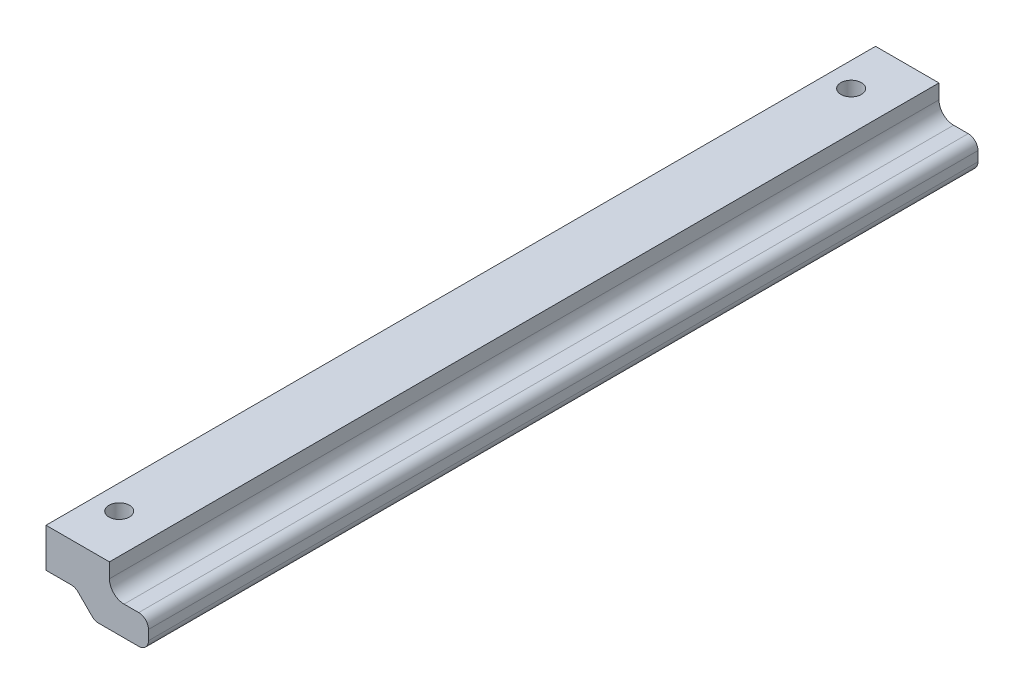
SolidWorks part; units mm, degrees
ref_plane "Front Plane" through (0, 0, 0) normal (0, 0, 1) x (1, 0, 0)
ref_plane "Top Plane" through (0, 0, 0) normal (0, 1, 0) x (1, 0, 0)
ref_plane "Right Plane" through (0, 0, 0) normal (1, 0, 0) x (0, 0, -1)
sketch "Sketch1" plane through (0, 0, 0) normal (0, 0, 1) x (1, 0, 0)
  line L1 (13, -6) -> (13, 0)
  line L2 (55, 0) -> (-55, 0) construction
  line L6 (13, -6) -> (21, -6)
  line L7 (21, -6) -> (21, -12)
  line L8 (0, 0) -> (13, 0)
  line L9 (21, -12) -> (10, -12)
  line L10 (10, -12) -> (6, -8)
  line L11 (6, -8) -> (0, -8)
  line L13 (0, -55) -> (0, 55) construction
  line L14 (0, -8) -> (0, 0)
  point P0 (9.4314, -8)
  dimension "D1" = 6
  dimension "D2" = 6
  dimension "D3" = 8
  dimension "D4" = 10
  dimension "D5" = 8
  dimension "D6" = 45
extrude "Boss-Extrude1" add sketch "Sketch1" against normal blind 170 contours L7 L6 region at (9.8798, -6.062, 0)
fillet "Fillet2" radius 3 1 edges at (13, -6, -85)
sketch "Sketch2" plane through (0, 0, 0) normal (0, 1, 0) x (1, 0, 0)
  line L0 (0, -55) -> (0, 55) construction
  line L1 (-55, 0) -> (55, 0) construction
  circle A0 centre (5, 10) radius 2.1
  circle A1 centre (5, 160) radius 2.1
  dimension "D3" = 4.2
  dimension "D1" = 5
  dimension "D2" = 10
  dimension "D4" = 150
extrude "Cut-Extrude1" cut sketch "Sketch2" against normal up to surface (8 mm away) up to face at (3, -8, -85)
sketch "Sketch3" plane through (0, 0, 0) normal (0, 1, 0) x (1, 0, 0)
  line L0 (0, -55) -> (0, 55) construction
  line L1 (1.55, 11.9919) -> (1.55, 8.0081)
  line L16 (1.55, 8.0081) -> (5, 6.0163)
  line L17 (5, 6.0163) -> (8.45, 8.0081)
  line L18 (8.45, 8.0081) -> (8.45, 11.9919)
  line L19 (8.45, 11.9919) -> (5, 13.9837)
  line L20 (5, 13.9837) -> (1.55, 11.9919)
  line L22 (1.55, 161.9919) -> (1.55, 158.0081)
  line L23 (1.55, 158.0081) -> (5, 156.0163)
  line L24 (5, 156.0163) -> (8.45, 158.0081)
  line L25 (8.45, 158.0081) -> (8.45, 161.9919)
  line L26 (8.45, 161.9919) -> (5, 163.9837)
  line L27 (5, 163.9837) -> (1.55, 161.9919)
  circle A2 centre (5, 10) radius 3.45 construction
  circle A3 centre (5, 160) radius 3.45 construction
  dimension "D1" = 6.9
  dimension "D2" = 6.9
extrude "Cut-Extrude2" cut sketch "Sketch3" along normal blind 8 from surface starting at face at (15.5, -12, -85)
fillet "Fillet3" radius 2 2 edges at (21, -12, -85) (21, -6, -85)
sketch "Sketch4" plane through (0, 0, 0) normal (-1, 0, 0) x (0, 0, 1)
  line L0 (-170, 0) -> (0, 0) construction
  line L1 (-41.4426, 0) -> (-33.4426, 0)
  line L2 (-41.4426, 0) -> (-41.4426, -5)
  line L3 (-41.4426, -5) -> (-33.4426, -5)
  line L4 (-33.4426, 0) -> (-33.4426, -5)
  dimension "D1" = 5
  dimension "D2" = 8
extrude "Cut-Extrude3" [suppressed] cut sketch "Sketch4" against normal up to surface (21 mm away) up to face at (21, -9, -85)
fillet "Fillet4" radius 2 4 edges at (6, -8, -166.7032) (6, -8, -85) (10, -12, -85) (6, -8, -3.2968)
